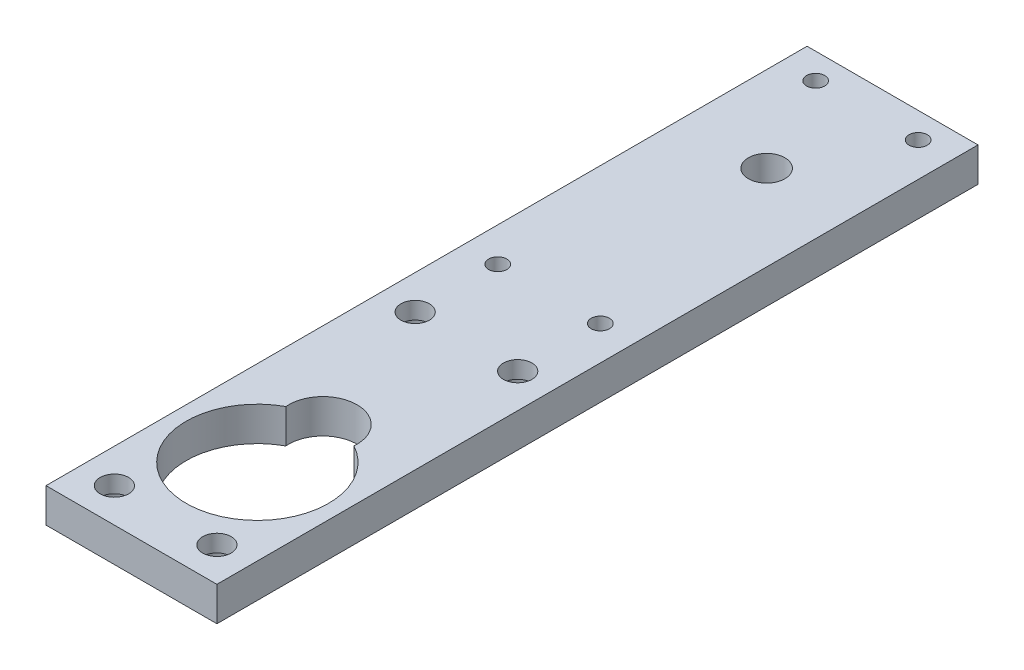
SolidWorks part; units mm, degrees
ref_plane "前视基准面" through (0, 0, 0) normal (0, 0, 1) x (1, 0, 0)
ref_plane "上视基准面" through (0, 0, 0) normal (0, 1, 0) x (1, 0, 0)
ref_plane "右视基准面" through (0, 0, 0) normal (1, 0, 0) x (0, 0, -1)
other "Configuration Table"
sketch "草图1" plane through (0, 0, 0) normal (0, 1, 0) x (1, 0, 0)
  line L1 (0, 0) -> (15, 0)
  line L2 (0, 0) -> (0, -32.4)
  line L3 (0, -32.4) -> (15, -32.4)
  line L4 (15, 0) -> (15, -32.4)
  line L9 (0, 2) -> (15, 2)
  line L10 (0, 2) -> (0, 34.4)
  line L11 (0, 34.4) -> (15, 34.4)
  line L12 (15, 2) -> (15, 34.4)
  line L17 (0, 0) -> (15, 0)
  line L18 (0, 0) -> (0, 2)
  line L19 (0, 2) -> (15, 2)
  line L20 (15, 0) -> (15, 2)
  circle A4 centre (3, -3) radius 1.25
  circle A5 centre (12, -3) radius 1.25
  circle A6 centre (3, -29.4) radius 1.25
  circle A7 centre (12, -29.4) radius 1.25
  circle A8 centre (7.5, -21.35) radius 6.25
  circle A9 centre (7.5, -15.6) radius 3
  circle A10 centre (3, -3) radius 2
  circle A11 centre (12, -3) radius 2
  circle A12 centre (3, -29.4) radius 2
  circle A13 centre (12, -29.4) radius 2
  circle A22 centre (3, 4.25) radius 1.3
  circle A23 centre (12, 4.25) radius 1.3
  circle A24 centre (3, 32.15) radius 1.3
  circle A25 centre (12, 32.15) radius 1.3
  circle A26 centre (3, 32.15) radius 0.8
  circle A27 centre (12, 32.15) radius 0.8
  circle A28 centre (3, 4.25) radius 0.8
  circle A29 centre (12, 4.25) radius 0.8
  circle A30 centre (7.5, 23.35) radius 1.6
  point P10 (7.5, -32.4)
  dimension "D3" = 2.5
  dimension "D8" = 4
  dimension "D6" = 12.5
  dimension "D7" = 6
  dimension "D12" = 2.6
  dimension "D13" = 1.6
  dimension "D14" = 3.2
  dimension "D1" = 3
  dimension "D2" = 15
  dimension "D4" = 11.05
  dimension "D5" = 5.75
  dimension "D9" = 3
  dimension "D10" = 3
  dimension "D11" = 3
  dimension "32.4" = 32.4
  dimension "D15" = 3
  dimension "D16" = 2.25
  dimension "D17" = 3
  dimension "D18" = 27.9
  dimension "D19" = 11.05
  dimension "D20" = 2
extrude "凸台-拉伸1" add sketch "草图1" along normal blind 3 contours L4 L3 L2 L1 | L20 L19 L18 L17 | L12 L11 L10 L9 | A4 | A5 | A9 | A8 | A6 | A7 | A28 | A29 | A30 | A26 | A27
extrude "切除-拉伸3" cut sketch "草图1<5>" along normal blind 1.5 contours A11 | A10 | A12 | A13 | A23 | A25 | A24 | A22
sketch "草图1<5>" plane through (0, 0, 0) normal (0, 1, 0) x (1, 0, 0) same geometry as "草图1"
